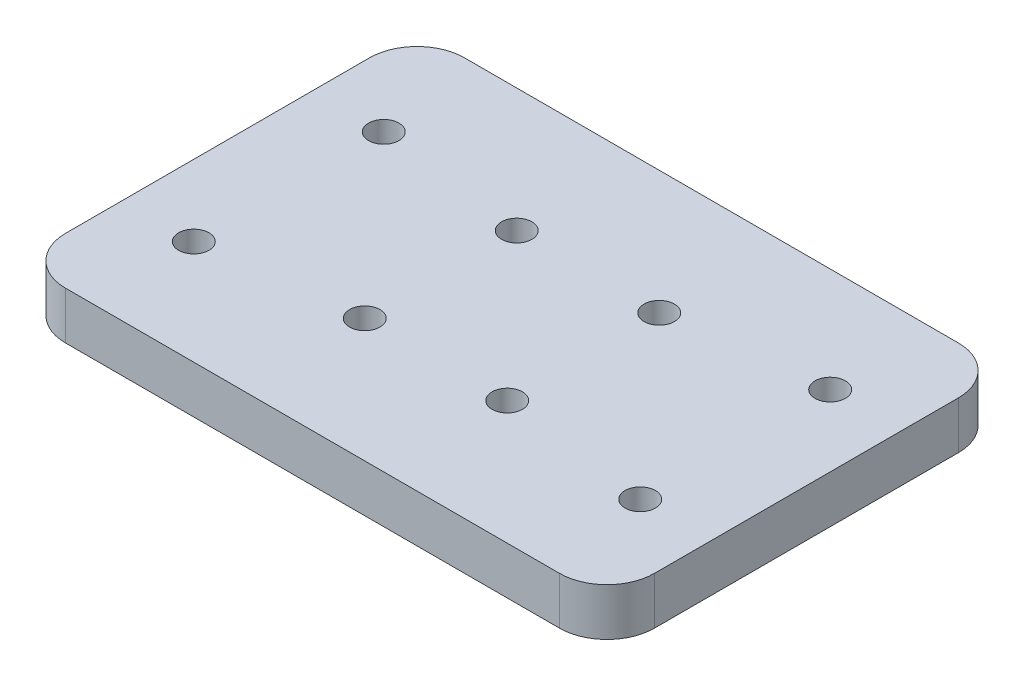
SolidWorks part; units mm, degrees
material "Acrylic (Medium-high impact)"
ref_plane "Front Plane" through (0, 0, 0) normal (0, 0, 1) x (1, 0, 0)
ref_plane "Top Plane" through (0, 0, 0) normal (0, 1, 0) x (1, 0, 0)
ref_plane "Right Plane" through (0, 0, 0) normal (1, 0, 0) x (0, 0, -1)
sketch "Sketch1" plane through (0, 0, 0) normal (0, 1, 0) x (1, 0, 0)
  line L0 (7.5, 42) -> (7.5, 0) construction
  line L1 (0, 0) -> (62, 0)
  line L2 (0, 0) -> (0, 42)
  line L3 (0, 42) -> (62, 42)
  line L4 (62, 0) -> (62, 42)
  line L5 (31, 42) -> (31, 0) construction
  line L6 (62, 21) -> (0, 21) construction
  circle A0 centre (7.5, 31) radius 1.6
  circle A1 centre (7.5, 11) radius 1.6
  circle A2 centre (54.5, 11) radius 1.6
  circle A3 centre (54.5, 31) radius 1.6
  dimension "D3" = 20
  dimension "D4" = 3.2
  dimension "D1" = 62
  dimension "D2" = 42
  dimension "D5" = 7.5
extrude "Boss-Extrude1" add sketch "Sketch1" along normal blind 5
sketch "Sketch2" plane through (0, 5, 0) normal (0, 1, 0) x (1, 0, 0)
  line L0 (31, 29) -> (31, 13) construction
  line L1 (23.5, 13) -> (38.5, 13) construction
  line L2 (23.5, 13) -> (23.5, 29) construction
  line L3 (23.5, 29) -> (38.5, 29) construction
  line L4 (38.5, 13) -> (38.5, 29) construction
  line L5 (0, 21) -> (62, 21) construction
  line L6 (0, 42) -> (0, 0) construction
  line L7 (62, 0) -> (62, 42) construction
  circle A0 centre (38.5, 29) radius 1.6
  circle A1 centre (38.5, 13) radius 1.6
  circle A2 centre (23.5, 13) radius 1.6
  circle A3 centre (23.5, 29) radius 1.6
  point P12 (31, 21)
  dimension "D1" = 3.2
  dimension "D2" = 16
  dimension "D3" = 15
extrude "Cut-Extrude1" cut sketch "Sketch2" against normal through all
fillet "Fillet1" radius 5 4 edges at (0, 2.5, -42) (62, 2.5, -42) (62, 2.5, 0) (0, 2.5, 0)
